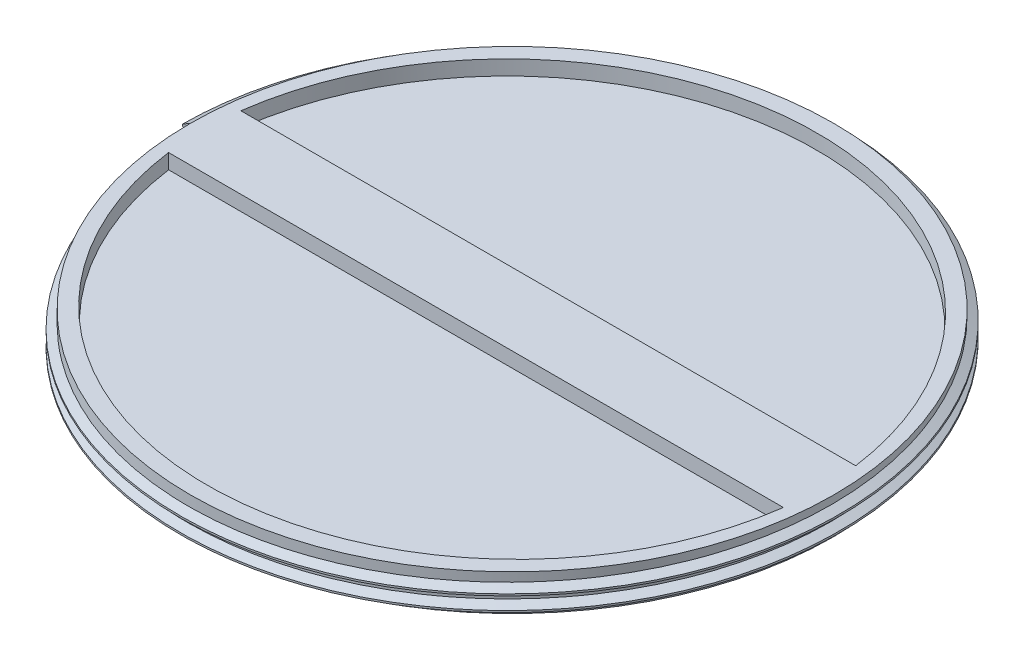
SolidWorks part; units mm, degrees
ref_plane "Front Plane" through (0, 0, 0) normal (0, 0, 1) x (1, 0, 0)
ref_plane "Top Plane" through (0, 0, 0) normal (0, 1, 0) x (1, 0, 0)
ref_plane "Right Plane" through (0, 0, 0) normal (1, 0, 0) x (0, 0, -1)
sketch "Sketch1" plane through (0, 0, 0) normal (0, 1, 0) x (1, 0, 0)
  circle A0 centre (0, 0) radius 44.5
  dimension "D1" = 89
extrude "Boss-Extrude2" add sketch "Sketch1" along normal blind 5
ref_plane "Plane1" through (0, 0, 45) normal (0, 0, 1) x (1, 0, 0)
thread "Thread1" pitch 2 method extrude profile "Thread Profile1" start angle 0, offset 0, length 4, pitch 2, diameter 89
ref_plane "Plane2" through (-44.5, 5, 0) normal (0, 0, 1) x (-1, 0, 0)
sketch "Thread Profile1" plane through (-44.5, 5, 0) normal (0, 0, 1) x (-1, 0, 0)
  line L0 (0, 0) -> (0, 2) construction
  line L1 (0, 0) -> (1.0825, 0.625)
  line L2 (1.0825, 0.625) -> (1.0825, 0.875)
  line L3 (1.0825, 0.875) -> (0, 1.5)
  line L4 (1.0825, 0.75) -> (0, 0.75) construction
  line L11 (0, 0) -> (0, 1.5)
  point P2 (0, 0)
  dimension "Pitch" = 2
  dimension "Profile_Angle" = 60
  dimension "Profile_Land" = 0.25
  dimension "Profile_Height" = 1.0825
ref_plane "Plane3" through (0, 0, 10) normal (0, 0, 1) x (1, 0, 0)
sketch "Sketch5" plane through (0, 5, 0) normal (0, 1, 0) x (1, 0, 0)
  line L1 (42.516, 5) -> (-42.516, 5) construction
  line L2 (42.516, 5) -> (42.516, -5) construction
  line L3 (42.516, -5) -> (-42.516, -5)
  line L4 (-42.516, 5) -> (-42.516, -5) construction
  line L5 (42.516, 5) -> (-42.516, -5) construction
  line L6 (42.516, -5) -> (-42.516, 5) construction
  arc A0 (-42.516, -5) -> (42.516, -5) centre (0, 0.7189) ccw
  point P0 (0, 0)
  dimension "D1" = 10
extrude "Cut-Extrude2" cut sketch "Sketch5" against normal blind 2 draft 2
mirror "Mirror1" about plane through (0, 0, 0) normal (0, 0, 1) of "Cut-Extrude2"
